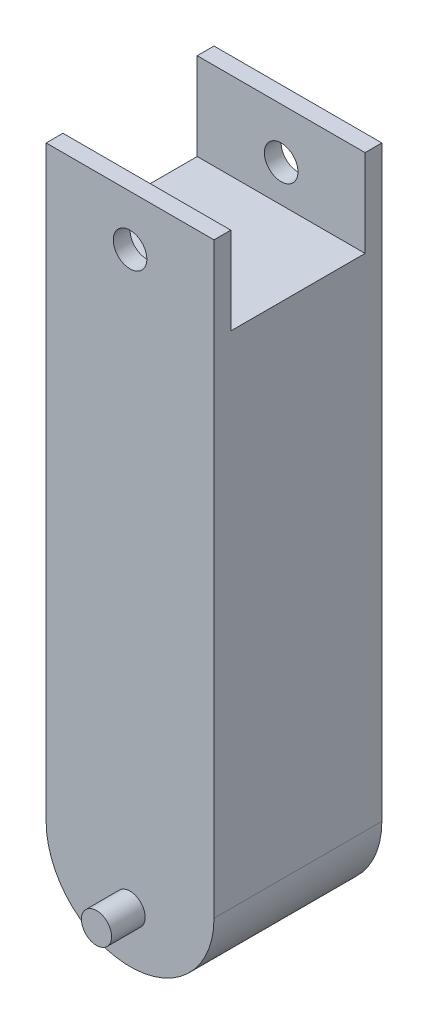
SolidWorks part; units mm, degrees
ref_plane "Front Plane" through (0, 0, 0) normal (0, 0, 1) x (1, 0, 0)
ref_plane "Top Plane" through (0, 0, 0) normal (0, 1, 0) x (1, 0, 0)
ref_plane "Right Plane" through (0, 0, 0) normal (1, 0, 0) x (0, 0, -1)
sketch "Sketch1" plane through (0, 0, 0) normal (0, 0, 1) x (1, 0, 0)
  line L1 (0, 0) -> (63.5, 0)
  line L2 (0, 0) -> (0, 254)
  line L3 (0, 254) -> (63.5, 254)
  line L4 (63.5, 0) -> (63.5, 254)
  dimension "D1" = 63.5
  dimension "D2" = 254
extrude "Boss-Extrude1" add sketch "Sketch1" along normal blind 63.5
fillet "Fillet1" 2 edges at (63.5, 0, 31.75) (0, 0, 31.75) type full round first side face at (63.5, 127, 31.75) second side face at (0, 127, 31.75) middle face at (31.75, 0, 31.75)
sketch "Sketch2" plane through (0, 0, 63.5) normal (0, 0, 1) x (1, 0, 0)
  line L0 (0, 31.75) -> (63.5, 31.75) construction
  line L1 (31.75, 254) -> (31.75, -22.5042) construction
  line L2 (63.5, 254) -> (0, 254) construction
  circle A0 centre (31.75, 19.05) radius 5.715
  arc A1 (0, 31.75) -> (63.5, 31.75) centre (31.75, 31.75) ccw construction
  point P13 (31.75, 19.2109)
  dimension "D2" = 11.43
  dimension "D1" = 12.7
extrude "Boss-Extrude2" add sketch "Sketch2" along normal blind 12.7
ref_plane "Plane1" through (0, 0, 31.75) normal (0, 0, 1) x (1, 0, 0)
mirror "Mirror1" about plane through (0, 0, 31.75) normal (0, 0, 1) of "Boss-Extrude2"
sketch "Sketch3" plane through (0, 0, 31.75) normal (0, 0, 1) x (1, 0, 0)
  line L0 (31.75, 19.05) -> (31.75, 161.4754) construction
  circle A0 centre (31.75, 234.95) radius 6.35
  point P4 (28.0584, 128.2512)
  point P5 (31.75, 19.05)
  dimension "D1" = 12.7
  dimension "D2" = 215.9
extrude "Cut-Extrude1" cut sketch "Sketch3" against normal blind 60.96 and the other way blind 84.836
sketch "Sketch4" plane through (0, 0, 0) normal (-1, 0, 0) x (0, 0, 1)
  line L0 (31.75, 179.8594) -> (31.75, -45.8878) construction
  line L1 (6.35, 220.98) -> (57.15, 220.98)
  line L2 (6.35, 220.98) -> (6.35, 275.2949)
  line L3 (6.35, 275.2949) -> (57.15, 275.2949)
  line L4 (57.15, 220.98) -> (57.15, 275.2949)
  line L5 (31.75, -34.925) -> (31.75, 34.925) construction
  line L7 (63.5, 254) -> (0, 254) construction
  dimension "D1" = 50.8
  dimension "D2" = 33.02
extrude "Cut-Extrude2" cut sketch "Sketch4" against normal blind 117.602 and the other way blind 69.596
ref_plane "Plane2" through (31.75, 0, 0) normal (-1, 0, 0) x (0, 0, 1)
